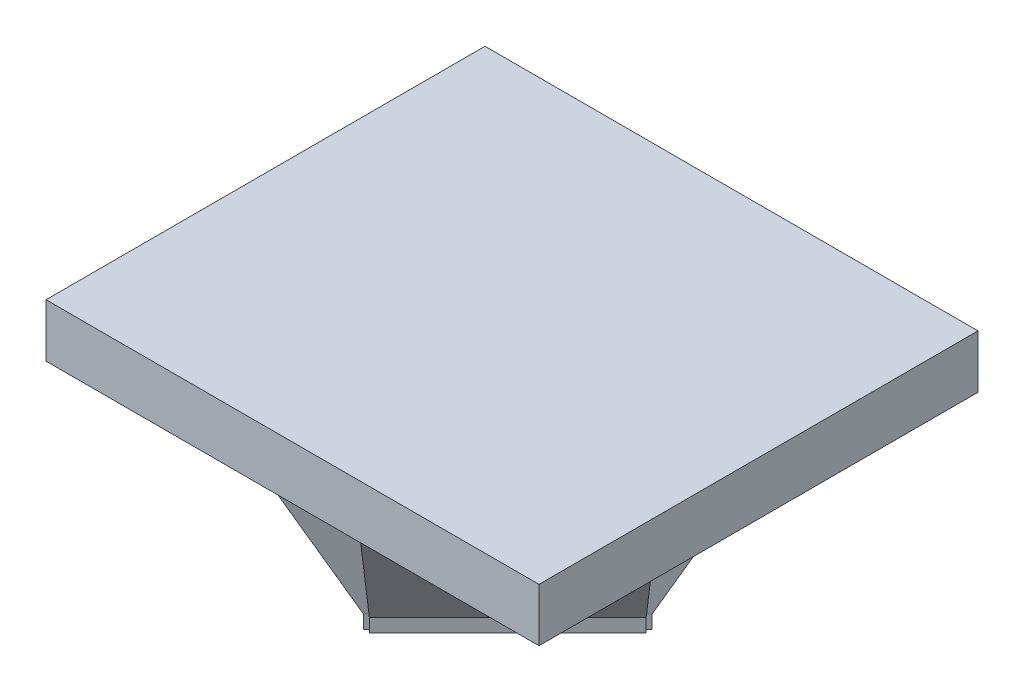
SolidWorks part; units mm, degrees
ref_plane "Front Plane" through (0, 0, 0) normal (0, 0, 1) x (1, 0, 0)
ref_plane "Top Plane" through (0, 0, 0) normal (0, 1, 0) x (1, 0, 0)
ref_plane "Right Plane" through (0, 0, 0) normal (1, 0, 0) x (0, 0, -1)
sketch "Sketch1" plane through (0, 0, 0) normal (0, 1, 0) x (1, 0, 0)
  line L1 (-46.6, 41.5) -> (46.6, 41.5)
  line L2 (-46.6, 41.5) -> (-46.6, -41.5)
  line L3 (-46.6, -41.5) -> (46.6, -41.5)
  line L4 (46.6, 41.5) -> (46.6, -41.5)
  line L5 (-46.6, 41.5) -> (46.6, -41.5) construction
  line L6 (-46.6, -41.5) -> (46.6, 41.5) construction
  point P0 (0, 0)
  dimension "D1" = 83
  dimension "D2" = 93.2
extrude "Boss-Extrude1" add sketch "Sketch1" against normal blind 10.05
sketch "Sketch2" plane through (0, -10.05, 0) normal (0, -1, 0) x (1, 0, 0)
  line L0 (-32.6387, 16.2823) -> (-17.0823, 31.8387) construction
  line L8 (-32.6387, 16.2823) -> (-17.0823, 31.8387) construction
  line L9 (-29.6334, 0.5492) -> (-37.942, 8.8577) construction
  line L10 (-29.6334, 0.5492) -> (-37.942, 8.8577) construction
  line L11 (-9.6577, 37.142) -> (-1.3492, 28.8334) construction
  line L12 (-9.6577, 37.142) -> (-1.3492, 28.8334) construction
  line L13 (15.4823, 31.8387) -> (31.0387, 16.2823) construction
  line L14 (15.4823, 31.8387) -> (31.0387, 16.2823) construction
  line L15 (-0.2508, 28.8334) -> (8.0577, 37.142) construction
  line L16 (-0.2508, 28.8334) -> (8.0577, 37.142) construction
  line L18 (36.342, 8.8577) -> (28.0334, 0.5492) construction
  line L19 (46.6, -41.5) -> (-46.6, 41.5) construction
  line L20 (36.342, 8.8577) -> (28.0334, 0.5492) construction
  line L21 (46.6, 41.5) -> (-46.6, -41.5) construction
  line L40 (31.0387, -16.2823) -> (15.4823, -31.8387) construction
  line L41 (31.0387, -16.2823) -> (15.4823, -31.8387) construction
  line L42 (28.0334, -0.5492) -> (36.342, -8.8577) construction
  line L43 (28.0334, -0.5492) -> (36.342, -8.8577) construction
  line L44 (8.0577, -37.142) -> (-0.2508, -28.8334) construction
  line L45 (8.0577, -37.142) -> (-0.2508, -28.8334) construction
  line L46 (-17.0823, -31.8387) -> (-32.6387, -16.2823) construction
  line L47 (-17.0823, -31.8387) -> (-32.6387, -16.2823) construction
  line L48 (-1.3492, -28.8334) -> (-9.6577, -37.142) construction
  line L49 (-1.3492, -28.8334) -> (-9.6577, -37.142) construction
  line L50 (-37.942, -8.8577) -> (-29.6334, -0.5492) construction
  line L51 (-37.942, -8.8577) -> (-29.6334, -0.5492) construction
  line L76 (-10.7183, -38.2026) -> (-0.8, -28.2843)
  line L77 (-0.8, -28.2843) -> (9.1183, -38.2026)
  line L78 (9.1183, -38.2026) -> (37.4026, -9.9183)
  line L79 (37.4026, -9.9183) -> (27.4843, 0)
  line L80 (27.4843, 0) -> (37.4026, 9.9183)
  line L81 (37.4026, 9.9183) -> (9.1183, 38.2026)
  line L82 (9.1183, 38.2026) -> (-0.8, 28.2843)
  line L83 (-0.8, 28.2843) -> (-10.7183, 38.2026)
  line L84 (-39.0026, 9.9183) -> (-10.7183, 38.2026)
  line L85 (-39.0026, 9.9183) -> (-29.0843, 0)
  line L86 (-29.0843, 0) -> (-39.0026, -9.9183)
  line L87 (-39.0026, -9.9183) -> (-10.7183, -38.2026)
  point P32 (0, 0)
  point P42 (0, 0)
ref_plane "Plane1" through (0, -36.25, 0) normal (0, -1, 0) x (-1, 0, 0)
sketch "Sketch3" plane through (0, -36.25, 0) normal (0, -1, 0) x (-1, 0, 0)
  line L0 (0.2508, 28.8334) -> (-28.0334, 0.5492) construction
  line L2 (1.3492, -28.8334) -> (29.6334, -0.5492) construction
  line L4 (-28.0334, -0.5492) -> (0.2508, -28.8334) construction
  line L5 (1.3492, 28.8334) -> (29.6334, 0.5492) construction
  line L6 (29.6334, -0.5492) -> (29.0843, 0) construction
  line L7 (29.0843, 0) -> (29.6334, 0.5492) construction
  line L8 (1.3492, 28.8334) -> (0.8, 28.2843) construction
  line L9 (0.8, 28.2843) -> (0.2508, 28.8334) construction
  line L10 (-28.0334, 0.5492) -> (-27.4843, 0) construction
  line L11 (-27.4843, 0) -> (-28.0334, -0.5492) construction
  line L12 (1.3492, -28.8334) -> (0.8, -28.2843) construction
  line L13 (0.8, -28.2843) -> (0.2508, -28.8334) construction
  line L14 (0.2508, 26.7121) -> (-25.9121, 0.5492)
  line L15 (-25.9121, 0.5492) -> (-25.363, 0)
  line L16 (-25.363, 0) -> (-25.9121, -0.5492)
  line L17 (-25.9121, -0.5492) -> (0.2508, -26.7121)
  line L18 (0.8, -26.163) -> (0.2508, -26.7121)
  line L19 (1.3492, -26.7121) -> (0.8, -26.163)
  line L20 (1.3492, -26.7121) -> (27.5121, -0.5492)
  line L21 (27.5121, -0.5492) -> (26.963, 0)
  line L22 (26.963, 0) -> (27.5121, 0.5492)
  line L23 (1.3492, 26.7121) -> (27.5121, 0.5492)
  line L24 (1.3492, 26.7121) -> (0.8, 26.163)
  line L25 (0.8, 26.163) -> (0.2508, 26.7121)
  dimension "D1" = 1.5
loft "Loft3" add profiles "Sketch3", "Sketch2" connector at (-0.8, -36.25, -26.163) connector at (-0.8, -10.05, -28.2843)
sketch "Sketch5" plane through (0, -36.25, 0) normal (0, -1, 0) x (1, 0, 0)
  line L12 (-0.8, -26.163) -> (-0.2508, -26.7121)
  line L13 (-0.2508, -26.7121) -> (25.9121, -0.5492)
  line L14 (25.9121, -0.5492) -> (25.363, 0)
  line L15 (25.363, 0) -> (25.9121, 0.5492)
  line L16 (25.9121, 0.5492) -> (-0.2508, 26.7121)
  line L17 (-0.2508, 26.7121) -> (-0.8, 26.163)
  line L18 (-0.8, 26.163) -> (-1.3492, 26.7121)
  line L19 (-1.3492, 26.7121) -> (-27.5121, 0.5492)
  line L20 (-27.5121, 0.5492) -> (-26.963, 0)
  line L21 (-26.963, 0) -> (-27.5121, -0.5492)
  line L22 (-27.5121, -0.5492) -> (-1.3492, -26.7121)
  line L23 (-1.3492, -26.7121) -> (-0.8, -26.163)
  line L24 (-0.8, -26.163) -> (-0.2508, -26.7121)
  line L25 (-0.2508, -26.7121) -> (25.9121, -0.5492)
  line L26 (25.9121, -0.5492) -> (25.363, 0)
  line L27 (25.363, 0) -> (25.9121, 0.5492)
  line L28 (25.9121, 0.5492) -> (-0.2508, 26.7121)
  line L29 (-0.2508, 26.7121) -> (-0.8, 26.163)
  line L30 (-0.8, 26.163) -> (-1.3492, 26.7121)
  line L31 (-1.3492, 26.7121) -> (-27.5121, 0.5492)
  line L32 (-27.5121, 0.5492) -> (-26.963, 0)
  line L33 (-26.963, 0) -> (-27.5121, -0.5492)
  line L34 (-27.5121, -0.5492) -> (-1.3492, -26.7121)
  line L35 (-1.3492, -26.7121) -> (-0.8, -26.163)
  dimension "D1" = 0
extrude "Boss-Extrude3" add sketch "Sketch5" along normal blind 2.5
